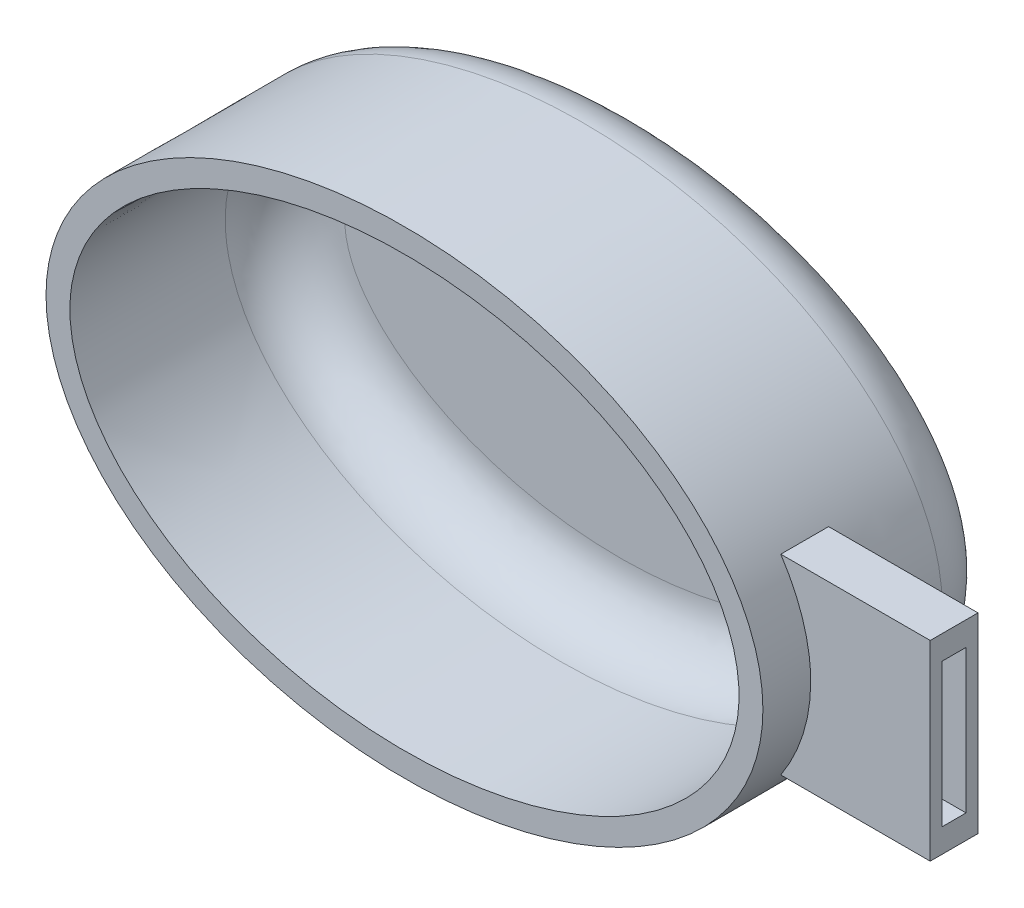
SolidWorks part; units mm, degrees
note: The reader was unsure of these and kept them because the rebuilt part matched: shared geometry of "Sketch3<3>".
ref_plane "Front Plane" through (0, 0, 0) normal (0, 0, 1) x (1, 0, 0)
ref_plane "Top Plane" through (0, 0, 0) normal (0, 1, 0) x (1, 0, 0)
ref_plane "Right Plane" through (0, 0, 0) normal (1, 0, 0) x (0, 0, -1)
sketch "Sketch1" plane through (0, 0, 0) normal (0, 0, 1) x (1, 0, 0)
  line L0 (0, 0) -> (30, 0) construction
  line L1 (30, 0) -> (4.5823, 0) construction
  ellipse E0 centre (0, 0) end of major axis (30, 0) minor radius 20
  dimension "D1" = 30
  dimension "D2" = 20
extrude "Boss-Extrude1" add sketch "Sketch1" along normal blind 20
shell "Shell1" thickness 2
fillet "Fillet3" radius 5 1 edges at (27.909, 1.4348, 2)
fillet "Fillet4" radius 5 1 edges at (30, 0, 0)
sketch "Sketch3" plane through (0, 0, 20) normal (0, 0, 1) x (1, 0, 0)
  line L0 (0, 0) -> (41.7937, 0) construction
  line L1 (40, 8) -> (40, -8)
  line L2 (40, -8) -> (27.4955, -8)
  line L3 (40, 8) -> (27.4955, 8)
  ellipse E0 centre (0, 0) end of major axis (30, 0) minor radius 20 construction
  ellipse E2 centre (0, 0) end of major axis (30, 0) minor radius 20
  ellipse E3 centre (0, 0) end of major axis (30, 0) minor radius 20 (27.4955, -8) -> (27.4955, 8) ccw
  dimension "D1" = 16
  dimension "D2" = 8
  dimension "D3" = 40
  dimension "D4" = 0
extrude "Boss-Extrude3" add sketch "Sketch3" against normal blind 8
extrude "Cut-Extrude2" cut sketch "Sketch3<3>" against normal blind 4
sketch "Sketch3<3>" plane through (0, 0, 20) normal (0, 0, 1) x (1, 0, 0) same geometry as "Sketch3"
sketch "Sketch12" plane through (40, 0, 0) normal (1, 0, 0) x (0, 0, -1)
  line L0 (-16, -8) -> (-16, 8) construction
  line L1 (-15, -6) -> (-13, -6)
  line L2 (-15, -6) -> (-15, 6)
  line L3 (-15, 6) -> (-13, 6)
  line L4 (-13, -6) -> (-13, 6)
  line L5 (-12, -8) -> (-16, -8) construction
  dimension "D1" = 12
  dimension "D2" = 2
  dimension "D3" = 1
  dimension "D4" = 2
extrude "Cut-Extrude3" cut sketch "Sketch12" against normal blind 20
